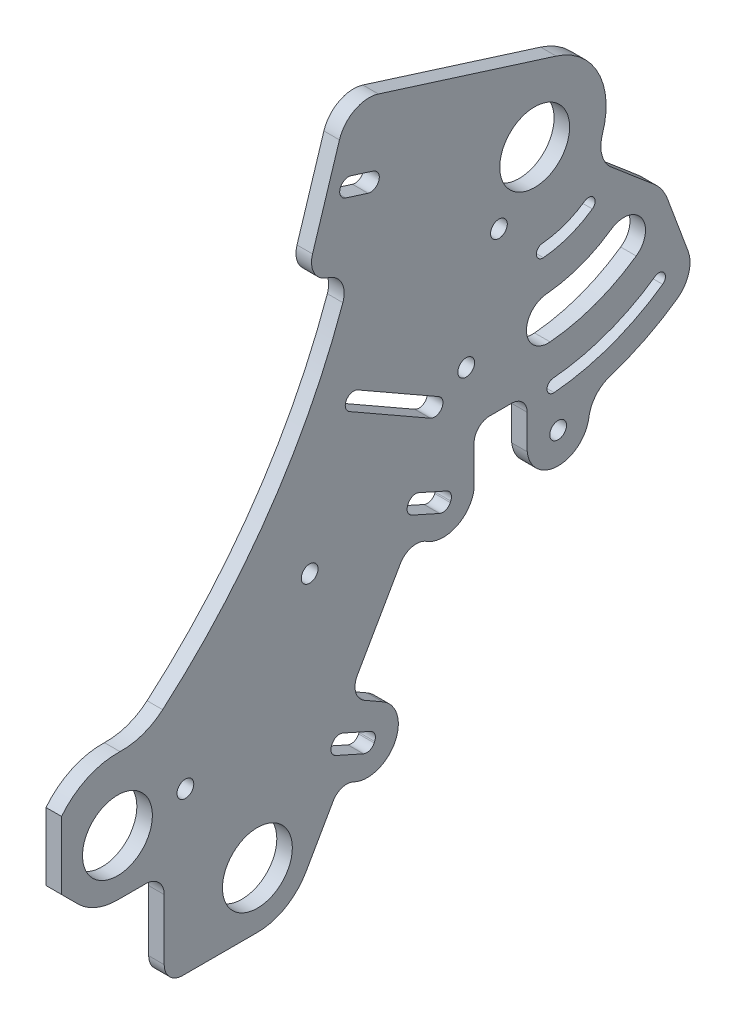
SolidWorks part; units mm, degrees
ref_plane "Front Plane" through (0, 0, 0) normal (0, 0, 1) x (1, 0, 0)
ref_plane "Top Plane" through (0, 0, 0) normal (0, 1, 0) x (1, 0, 0)
ref_plane "Right Plane" through (0, 0, 0) normal (1, 0, 0) x (0, 0, -1)
sketch "Sketch1" plane through (0, 0, 0) normal (1, 0, 0) x (0, 0, -1)
  line L0 (0, 0) -> (-57.2178, 40.0643) construction
  line L1 (55, 0) -> (-55, 0) construction
  line L2 (0, 0) -> (113.3671, 198.5091) construction
  line L3 (113.3671, 198.5091) -> (49.679, 218.5899) construction
  line L4 (99.338, 182.3162) -> (24.13, 14.224) construction
  line L5 (30.5555, 28.5852) -> (30.3602, 28.1486)
  line L6 (36.1341, 219.132) -> (45.2183, 216.2678)
  line L7 (38.2727, 225.9148) -> (47.3569, 223.0506)
  line L8 (34.9378, 30.2582) -> (46.2714, 25.1873)
  line L9 (47.9444, 20.8051) -> (47.749, 20.3685)
  line L10 (43.3668, 18.6955) -> (32.0332, 23.7664)
  line L11 (113.3671, 198.5091) -> (121.0867, 110.2733) construction
  line L12 (113.3671, 198.5091) -> (164.1704, 125.9544) construction
  line L13 (0, 55) -> (0, -55) construction
  line L14 (61.6761, 98.1406) -> (61.4807, 97.704)
  line L15 (66.0583, 99.8136) -> (77.3919, 94.7427)
  line L16 (79.0649, 90.3605) -> (78.8696, 89.9239)
  line L17 (74.4873, 88.2509) -> (63.1537, 93.3218)
  line L18 (72.429, 126.8253) -> (39.3441, 145.7198) construction
  line L19 (98.7442, 176.9048) -> (85.3778, 134.5121) construction
  line L20 (70.7285, 123.8476) -> (37.6436, 142.7421)
  line L21 (74.1295, 129.8029) -> (41.0446, 148.6974)
  line L22 (85.3778, 134.5121) -> (54.8261, 37.6144) construction
  circle A0 centre (0, 0) radius 14.2875
  circle A1 centre (-57.2178, 40.0643) radius 14.2875
  circle A2 centre (113.3671, 198.5091) radius 14.2875
  arc A3 (45.2183, 216.2678) -> (47.3569, 223.0506) centre (46.2876, 219.6592) ccw
  arc A4 (38.2727, 225.9148) -> (36.1341, 219.132) centre (37.2034, 222.5234) ccw
  arc A5 (118.1267, 144.1069) -> (119.6763, 126.3946) centre (118.9015, 135.2507) ccw
  arc A6 (116.4838, 162.8851) -> (116.9487, 157.5713) centre (116.7162, 160.2282) ccw
  arc A7 (120.8543, 112.9301) -> (121.3192, 107.6164) centre (121.0867, 110.2733) ccw
  arc A8 (154.8883, 139.2107) -> (144.6901, 153.7752) centre (149.7892, 146.4929) ccw
  arc A9 (136.9377, 164.8468) -> (133.8783, 169.2161) centre (135.408, 167.0314) ccw
  arc A10 (165.7001, 123.7698) -> (162.6407, 128.1391) centre (164.1704, 125.9544) ccw
  arc A11 (144.6901, 153.7752) -> (118.1267, 144.1069) centre (113.3671, 198.5091) cw
  arc A12 (154.8883, 139.2107) -> (119.6763, 126.3946) centre (113.3671, 198.5091) cw
  arc A13 (133.8783, 169.2161) -> (116.4838, 162.8851) centre (113.3671, 198.5091) cw
  arc A14 (136.9377, 164.8468) -> (116.9487, 157.5713) centre (113.3671, 198.5091) cw
  arc A15 (162.6407, 128.1391) -> (120.8543, 112.9301) centre (113.3671, 198.5091) cw
  arc A16 (165.7001, 123.7698) -> (121.3192, 107.6164) centre (113.3671, 198.5091) cw
  arc A17 (46.2714, 25.1873) -> (47.9444, 20.8051) centre (44.9167, 22.1597) cw
  arc A18 (47.749, 20.3685) -> (43.3668, 18.6955) centre (44.7214, 21.7231) cw
  arc A19 (32.0332, 23.7664) -> (30.3602, 28.1486) centre (33.3878, 26.794) cw
  arc A20 (30.5555, 28.5852) -> (34.9378, 30.2582) centre (33.5831, 27.2306) cw
  arc A21 (74.4873, 88.2509) -> (78.8696, 89.9239) centre (75.842, 91.2785) ccw
  arc A22 (79.0649, 90.3605) -> (77.3919, 94.7427) centre (76.0373, 91.7151) ccw
  arc A23 (63.1537, 93.3218) -> (61.4807, 97.704) centre (64.5084, 96.3494) cw
  arc A24 (61.6761, 98.1406) -> (66.0583, 99.8136) centre (64.7037, 96.786) cw
  circle A25 centre (-29.4365, 42.7262) radius 3.429
  circle A26 centre (21.3635, 93.5262) radius 3.429
  circle A27 centre (122.9635, 93.5262) radius 3.429
  arc A28 (70.7285, 123.8476) -> (74.1295, 129.8029) centre (72.429, 126.8253) ccw
  arc A29 (41.0446, 148.6974) -> (37.6436, 142.7421) centre (39.3441, 145.7198) ccw
  circle A30 centre (98.7442, 176.9048) radius 3.429
  circle A31 centre (85.3778, 134.5121) radius 3.429
  point P47 (49.299, 23.8327)
  point P54 (29.0056, 25.121)
  point P57 (31.9101, 31.6128)
  point P62 (80.4195, 93.3881)
  point P65 (60.1261, 94.6764)
  point P68 (63.0307, 101.1682)
  point P78 (55.8866, 136.2725)
  dimension "D2" = 28.575
  dimension "D4" = 228.6
  dimension "D10" = 13.081
  dimension "D7" = 3.556
  dimension "D8" = 9.525
  dimension "D11" = 65.895
  dimension "D18" = 91.2399
  dimension "D20" = 5.334
  dimension "D21" = 25.0729
  dimension "D27" = 7.112
  dimension "D22" = 8.89
  dimension "D29" = 3.3168
  dimension "D30" = 6.858
  dimension "D33" = 6.858
  dimension "D36" = 6.858
  dimension "D40" = 3.429
  dimension "D43" = 6.858
  dimension "D44" = 6.858
  dimension "D46" = 31.75
  dimension "D1" = 35
  dimension "D3" = 69.85
  dimension "D5" = 60.27
  dimension "D6" = 17.5
  dimension "D9" = 66.7788
  dimension "D12" = 14.224
  dimension "D13" = 184.15
  dimension "D14" = 24.13
  dimension "D15" = 7.112
  dimension "D16" = 165.1
  dimension "D17" = 19.05
  dimension "D19" = 63.5
  dimension "D23" = 19.05
  dimension "D24" = 25.0729
  dimension "D25" = 5
  dimension "D26" = 35
  dimension "D28" = 88.9
  dimension "D31" = 27.7812
  dimension "D32" = 2.6619
  dimension "D34" = 78.5812
  dimension "D35" = 53.4619
  dimension "D37" = 180.1812
  dimension "D38" = 53.4619
  dimension "D39" = 82.55
  dimension "D41" = 38.1
  dimension "D42" = 69.85
  dimension "D45" = 44.45
  dimension "D47" = 101.6
sketch "Sketch2" plane through (0, 0, 0) normal (1, 0, 0) x (0, 0, -1)
  line L1 (-80.0778, 30.5954) -> (-80.0778, 58.2479)
  line L2 (19.8509, -11.3367) -> (31.0118, 8.2063)
  line L3 (0, 0) -> (113.3671, 198.5091) construction
  line L7 (167.6526, 153.1112) -> (176.0793, 130.3666)
  line L8 (144.0118, 176.3866) -> (162.118, 161.0155)
  line L9 (113.3671, 198.5091) -> (49.679, 218.5899) construction
  line L11 (49.4775, 249.281) -> (122.1507, 226.3672)
  line L12 (33.5463, 240.9877) -> (22.5477, 206.1046)
  line L13 (28.5188, 194.6341) -> (29.0827, 194.4563)
  line L14 (110.3329, 92.1997) -> (110.288, 92.1997)
  line L15 (88.5941, 92.1997) -> (88.5941, 106.1697)
  line L16 (110.288, 92.1997) -> (110.288, 106.1697)
  line L17 (103.938, 112.5197) -> (94.9441, 112.5197)
  line L18 (88.5941, 92.1997) -> (88.5941, 89.8131)
  line L19 (58.4048, 78.4274) -> (40.9124, 47.8643)
  line L20 (43.7407, 37.4658) -> (51.2253, 33.1821)
  line L23 (-38.1, 9.5843) -> (-38.1, -15.24)
  line L24 (-30.48, -22.86) -> (0, -22.86)
  line L25 (-57.2178, 17.2043) -> (-45.72, 17.2043)
  line L26 (-73.3822, 23.8999) -> (-80.0778, 30.5954)
  arc A1 (0, -22.86) -> (19.8509, -11.3367) centre (0, 0) ccw
  arc A2 (39.3228, 10.758) -> (51.2253, 33.1821) centre (44.9167, 22.1597) ccw
  arc A3 (69.1503, 81.0446) -> (88.5941, 89.8131) centre (76.0373, 91.7151) ccw
  arc A7 (31.0118, 8.2063) -> (39.3228, 10.758) centre (36.5259, 5.0572) cw
  arc A9 (171.4548, 115.5512) -> (176.0793, 130.3666) centre (164.1704, 125.9544) ccw
  arc A10 (171.4548, 115.5512) -> (144.2404, 102.0569) centre (113.3671, 198.5091) cw
  arc A11 (167.6526, 153.1112) -> (162.118, 161.0155) centre (149.7892, 146.4929) ccw
  arc A13 (141.0737, 189.2588) -> (122.1507, 226.3672) centre (113.3671, 198.5091) ccw
  arc A14 (144.0118, 176.3866) -> (141.0737, 189.2588) centre (153.1201, 185.237) cw
  arc A15 (33.5463, 240.9877) -> (49.4775, 249.281) centre (45.6585, 237.1687) cw
  arc A16 (34.9451, 182.6622) -> (-38.7381, 75.3772) centre (-204.3307, 268.0513) cw
  arc A17 (-56.1886, 69.2562) -> (-80.0778, 58.2479) centre (-57.2178, 40.0643) ccw
  arc A18 (29.0827, 194.4563) -> (34.9451, 182.6622) centre (26.3331, 185.7355) cw
  arc A19 (22.5477, 206.1046) -> (28.5188, 194.6341) centre (31.2685, 203.3549) ccw
  arc A21 (-38.7381, 75.3772) -> (-56.1886, 69.2562) centre (-55.2938, 94.6404) cw
  arc A22 (110.3329, 92.1997) -> (135.5378, 91.7438) centre (122.9635, 93.5262) ccw
  arc A24 (135.5378, 91.7438) -> (144.2404, 102.0569) centre (148.1121, 89.9614) cw
  arc A25 (110.288, 106.1697) -> (103.938, 112.5197) centre (103.938, 106.1697) ccw
  arc A26 (88.5941, 106.1697) -> (94.9441, 112.5197) centre (94.9441, 106.1697) cw
  arc A27 (58.4048, 78.4274) -> (69.1503, 81.0446) centre (65.0182, 74.6423) cw
  arc A28 (43.7407, 37.4658) -> (40.9124, 47.8643) centre (47.5258, 44.0792) cw
  arc A29 (-73.3822, 23.8999) -> (-57.2178, 17.2043) centre (-57.2178, 40.0643) ccw
  arc A30 (-30.48, -22.86) -> (-38.1, -15.24) centre (-30.48, -15.24) cw
  arc A31 (-38.1, 9.5843) -> (-45.72, 17.2043) centre (-45.72, 9.5843) ccw
  point P24 (84.2401, 101.4107)
  point P25 (-38.1, -22.86)
  point P27 (71.8548, 79.7236)
  point P30 (46.1964, 34.7951)
  point P41 (110.288, 112.5197)
  point P59 (-80.0778, 31.5898)
  point P62 (37.3653, 253.0999)
  point P66 (37.9664, 191.6553)
  point P69 (19.798, 197.3838)
  point P71 (88.5941, 112.5197)
  point P74 (-48.0067, 67.784)
  point P92 (37.1273, 41.2509)
  dimension "D2" = 45.72
  dimension "D4" = 25.4
  dimension "D5" = 21.6939
  dimension "D6" = 38.1
  dimension "D7" = 25.4
  dimension "D8" = 101.2729
  dimension "D9" = 38.1
  dimension "D10" = 6.35
  dimension "D11" = 58.42
  dimension "D13" = 12.7
  dimension "D15" = 12.7
  dimension "D17" = 9.144
  dimension "D18" = 254.0555
  dimension "D19" = 2.3866
  dimension "D20" = 25.4
  dimension "D21" = 25.4
  dimension "D24" = 12.7
  dimension "D28" = 6.35
  dimension "D30" = 7.62
  dimension "D31" = 7.62
  dimension "D33" = 22.86
  dimension "D34" = 29.21
  dimension "D35" = 7.62
  dimension "D3" = 22.86
  dimension "D12" = 88.9
  dimension "D14" = 58.42
  dimension "D16" = 19.05
  dimension "D22" = 180.1812
  dimension "D23" = 53.4619
  dimension "D25" = 20.32
  dimension "D26" = 20.32
  dimension "D27" = 12.6305
  dimension "D29" = 16.2437
  dimension "D32" = 35.2148
  dimension "D36" = 9.4689
extrude "Boss-Extrude1" add sketch "Sketch2" along normal blind 3.175 and the other way blind 3.175
extrude "Cut-Extrude1" cut sketch "Sketch1" against normal through all and the other way through all
